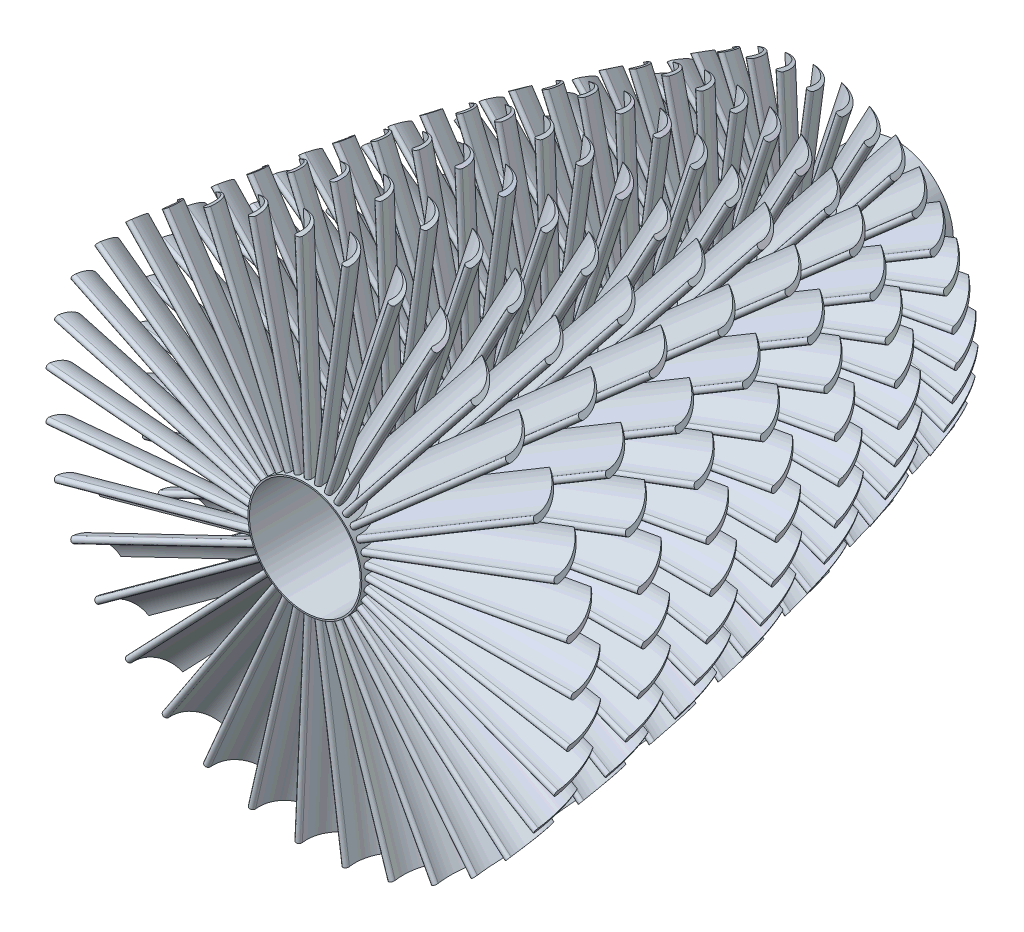
SolidWorks part; units mm, degrees
material "1060 Alloy"
ref_plane "Front Plane" through (0, 0, 0) normal (0, 0, 1) x (1, 0, 0)
ref_plane "Top Plane" through (0, 0, 0) normal (0, 1, 0) x (1, 0, 0)
ref_plane "Right Plane" through (0, 0, 0) normal (1, 0, 0) x (0, 0, -1)
sketch "Sketch1" plane through (0, 0, 0) normal (0, 0, 1) x (1, 0, 0)
  circle A0 centre (0, 0) radius 7.5
  dimension "D1" = 15
extrude "Extrude-Thin1" add sketch "Sketch1" along normal blind 80 thin
ref_plane "Plane1" through (7.7, 0, 0) normal (1, 0, 0) x (0, 0, -1)
sketch "Sketch2" plane through (7.7, 0, 0) normal (1, 0, 0) x (0, 0, -1)
  line L0 (-80, 0) -> (-53.0238, 0) construction
  line L1 (-80, 7.7) -> (-80, -7.7) construction
  line L2 (-75, 3.64) -> (-75, 3.45)
  arc A0 (-79.1474, 0.4094) -> (-79.1414, -0.409) centre (-79.17, 0) ccw
  arc A1 (-79.1474, 0.4094) -> (-75, 3.64) centre (-78.9265, 4.4033) ccw
  arc A2 (-79.1414, -0.409) -> (-75, 3.45) centre (-79.4557, 4.08) ccw
  dimension "D1" = 0.82
  dimension "D4" = 4
  dimension "D5" = 4.5
  dimension "D2" = 0.83
  dimension "D3" = 0.19
  dimension "D6" = 5
  dimension "D7" = 3.45
ref_plane "Plane2" through (51.2, 0, 0) normal (1, 0, 0) x (0, 0, -1)
sketch "Sketch3" plane through (51.2, 0, 0) normal (1, 0, 0) x (0, 0, -1)
  line L0 (-75, 3.64) -> (-75, 3.45) construction
  line L1 (-75, 3.64) -> (-75, 3.45)
  arc A0 (-79.1474, 0.4094) -> (-75, 3.64) centre (-78.9265, 4.4033) ccw construction
  arc A1 (-79.1474, 0.4094) -> (-79.1414, -0.409) centre (-79.17, 0) ccw construction
  arc A2 (-79.1414, -0.409) -> (-75, 3.45) centre (-79.4557, 4.08) ccw construction
  arc A3 (-79.1474, 0.4094) -> (-75, 3.64) centre (-78.9265, 4.4033) ccw
  arc A4 (-79.1474, 0.4094) -> (-79.1414, -0.409) centre (-79.17, 0) ccw
  arc A5 (-79.1414, -0.409) -> (-75, 3.45) centre (-79.4557, 4.08) ccw
extrude "Boss-Extrude1" add sketch "Sketch3" against normal up to surface (43.5109 mm away) separate body
pattern_linear "LPattern1" count 7 spacing 10.75 along (0, 0, -1) of bodies 102
sketch "Sketch4" plane through (0, 0, 0) normal (0, 1, 0) x (1, 0, 0)
  line L0 (18, 0) -> (78.8431, 0)
  line L1 (78.8431, 0) -> (78.8431, -88.7819)
  line L2 (78.8431, -88.7819) -> (36.3, -88.7819)
  line L3 (0, 0) -> (0, -115.0374) construction
  arc A0 (18, 0) -> (36.3, -88.7819) centre (-294.0702, -110.6018) cw
  dimension "D3" = 331.09
  dimension "D1" = 18
  dimension "D2" = 36.3
revolve "Cut-Revolve1" cut sketch "Sketch4" angle 360 about L3
pattern_circular "CirPattern1" count 35 over 360 about axis through (0, 0, 0) along (0, 0, 1)
